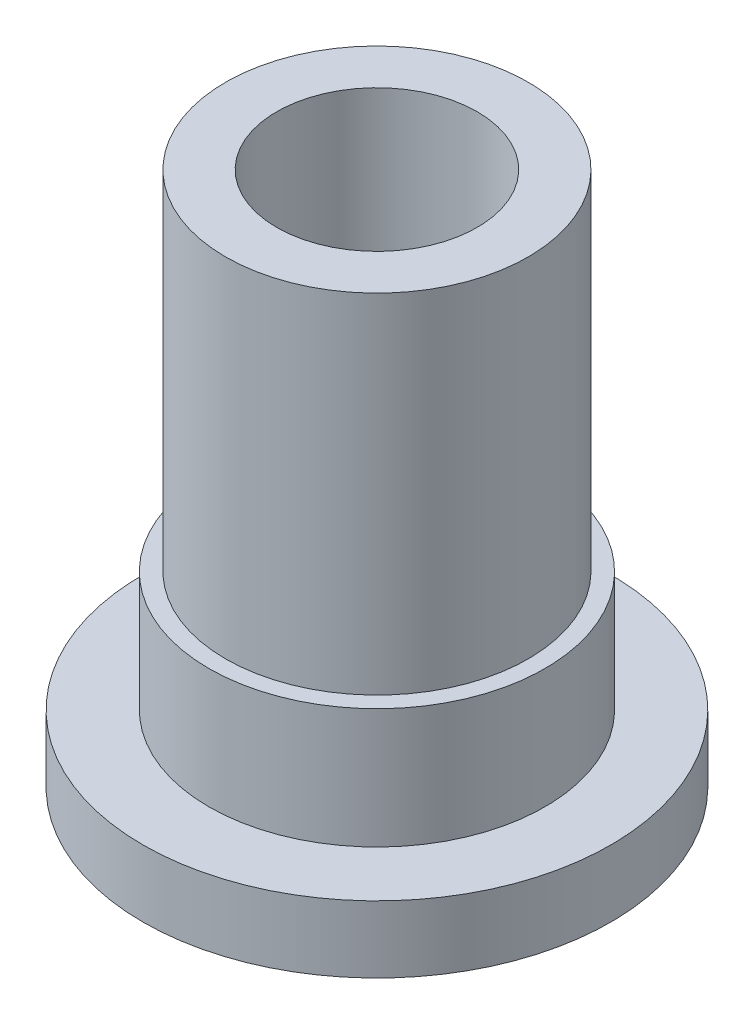
SolidWorks part; units mm, degrees
material "6061 Alloy"
ref_plane "Front Plane" through (0, 0, 0) normal (0, 0, 1) x (1, 0, 0)
ref_plane "Top Plane" through (0, 0, 0) normal (0, 1, 0) x (1, 0, 0)
ref_plane "Right Plane" through (0, 0, 0) normal (1, 0, 0) x (0, 0, -1)
sketch "Sketch1" plane through (0, 0, 0) normal (0, 1, 0) x (1, 0, 0)
  circle A0 centre (0, 0) radius 5.5562
  dimension "D1" = 11.1125
extrude "Boss-Extrude1" add sketch "Sketch1" along normal blind 1.5875
sketch "Sketch2" plane through (0, 1.5875, 0) normal (0, 1, 0) x (1, 0, 0)
  circle A1 centre (0, 0) radius 3.9903
  dimension "D2" = 7.9807
extrude "Boss-Extrude2" add sketch "Sketch2" along normal blind 11.1125 contours A1 region at (0, 1.5875, 0)
sketch "Sketch3" plane through (0, 12.7, 0) normal (0, 1, 0) x (1, 0, 0)
  circle A0 centre (0, 0) radius 2.3813
  dimension "D1" = 4.7625
extrude "Cut-Extrude1" cut sketch "Sketch3" against normal up to surface (12.7 mm away) contours A0 region at (0, 12.7, 0) up to face at (0, 0, 5.5562)
sketch "Sketch4" plane through (0, 12.7, 0) normal (0, 1, 0) x (1, 0, 0)
  circle A0 centre (0, 0) radius 3.5941
  circle A1 centre (0, 0) radius 3.9903 construction
  circle A2 centre (0, 0) radius 3.9903
  dimension "D1" = 7.1882
extrude "Cut-Extrude2" cut sketch "Sketch4" against normal blind 8.2677
equation "\"D1@Boss-Extrude2\"=1/2-1/16"
equation "\"D1@Cut-Extrude2\"=0.438-0.1125"
